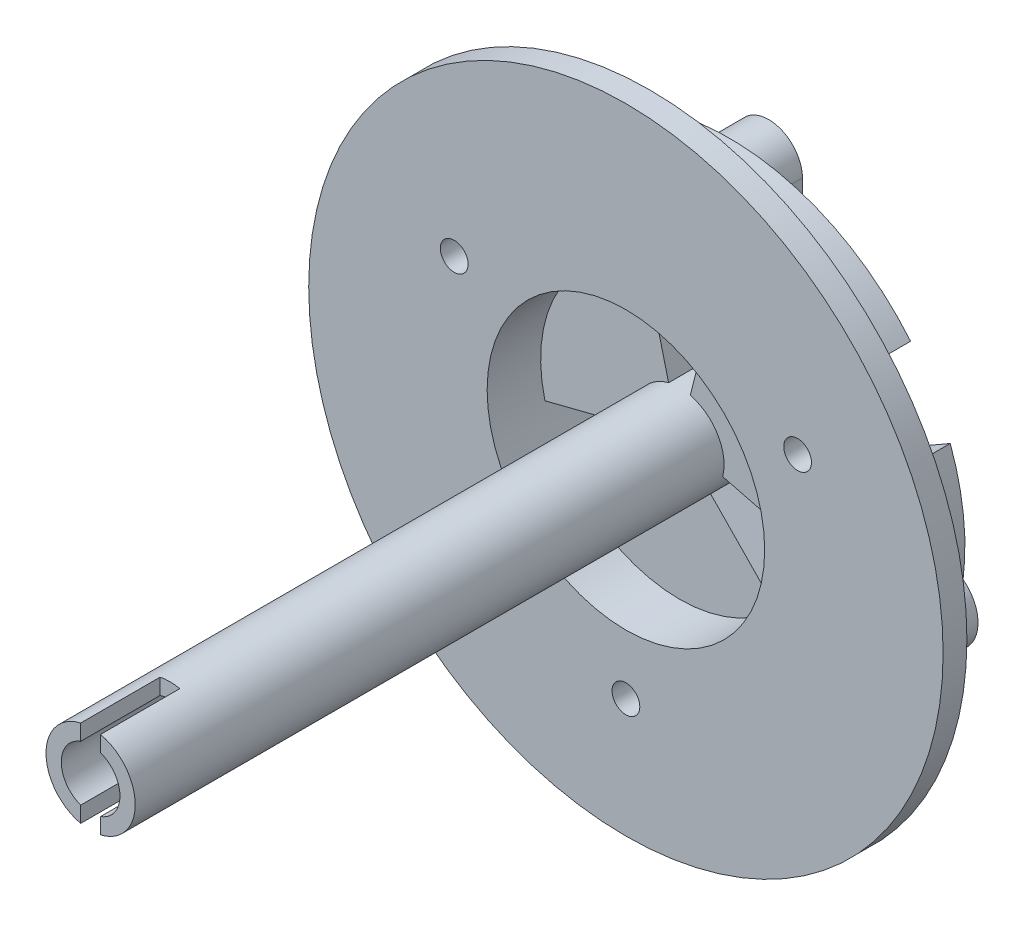
SolidWorks part; units mm, degrees
ref_plane "前视基准面" through (0, 0, 0) normal (0, 0, 1) x (1, 0, 0)
ref_plane "上视基准面" through (0, 0, 0) normal (0, 1, 0) x (1, 0, 0)
ref_plane "右视基准面" through (0, 0, 0) normal (1, 0, 0) x (0, 0, -1)
sketch "草图1" plane through (0, 0, 0) normal (0, 0, 1) x (1, 0, 0)
  circle A0 centre (0, 0) radius 16
extrude "凸台-拉伸1" add sketch "草图1" along normal blind 1.2
sketch "草图2" plane through (0, 0, 1.2) normal (0, 0, 1) x (1, 0, 0)
  circle A0 centre (0, 0) radius 7
extrude "切除-拉伸1" cut sketch "草图2" against normal blind 1.2
sketch "草图3" plane through (0, 0, 1.2) normal (0, 0, 1) x (1, 0, 0)
  circle A2 centre (8.6603, 5) radius 0.7
  circle A3 centre (0, -10) radius 0.7
  circle A4 centre (-8.6603, 5) radius 0.7
extrude "切除-拉伸2" cut sketch "草图3" against normal blind 1.2
sketch "草图4" plane through (0, 0, 0) normal (0, 0, -1) x (-1, 0, 0)
  line L3 (1.7039, 10) -> (1.7039, 5.3952)
  line L16 (-5.5379, -1.0034) -> (-3.6379, -4.2943)
  line L17 (3.6379, -4.2943) -> (5.5379, -1.0034)
  line L18 (1.7039, 5.3952) -> (-1.7039, 5.3952)
  line L19 (-5.5379, -1.0034) -> (-9.6103, -3.3546)
  line L21 (3.6379, -4.2943) -> (7.7103, -6.6454)
  line L25 (-3.6379, -4.2943) -> (-7.7103, -6.6454)
  line L31 (5.5379, -1.0034) -> (9.6103, -3.3546)
  line L32 (-1.7039, 5.3952) -> (-1.7039, 10)
  circle A1 centre (8.6603, -5) radius 0.9
  circle A2 centre (-8.6603, -5) radius 0.9
  circle A3 centre (0, 10) radius 0.9
  arc A4 (1.7039, 10) -> (-1.7039, 10) centre (0, 10) ccw
  arc A5 (7.7103, -6.6454) -> (9.6103, -3.3546) centre (8.6603, -5) ccw
  arc A6 (-9.6103, -3.3546) -> (-7.7103, -6.6454) centre (-8.6603, -5) ccw
extrude "凸台-拉伸2" add sketch "草图4" along normal blind 6
sketch "草图5" plane through (0, 0, 1.2) normal (0, 0, 1) x (1, 0, 0)
  circle A0 centre (0, 0) radius 7
extrude "切除-拉伸3" cut sketch "草图5" against normal blind 11
sketch "草图6" plane through (0, 0, 0) normal (0, 0, -1) x (-1, 0, 0)
  circle A0 centre (0, 0) radius 11.9
  circle A1 centre (0, 0) radius 7
extrude "凸台-拉伸3" add sketch "草图6" along normal blind 4
sketch "草图7" plane through (0, 0, 1.2) normal (0, 0, 1) x (1, 0, 0)
  circle A0 centre (-8.6603, 5) radius 0.7
  circle A1 centre (8.6603, 5) radius 0.7
  circle A2 centre (0, -10) radius 0.7
extrude "切除-拉伸4" cut sketch "草图7" against normal blind 13
sketch "草图8" plane through (0, 0, -4) normal (0, 0, -1) x (-1, 0, 0)
  circle A0 centre (0, 0) radius 2.25
extrude "凸台-拉伸4" add sketch "草图8" against normal blind 33 separate body
sketch "草图9" plane through (0, 0, -4) normal (0, 0, -1) x (-1, 0, 0)
  line L0 (-1.57, -1.6117) -> (-4.8846, -5.0141)
  line L1 (1.57, -1.6117) -> (4.8846, -5.0141)
  line L2 (-2.1808, -0.5539) -> (-6.7846, -1.7232)
  line L3 (-0.5477, 2.1823) -> (-1.7039, 6.7895)
  line L4 (0.5477, 2.1823) -> (1.7039, 6.7895)
  line L5 (2.1808, -0.5539) -> (6.7846, -1.7232)
  arc A0 (-4.8846, -5.0141) -> (4.8846, -5.0141) centre (0, 0) ccw
  arc A1 (-1.7039, 6.7895) -> (-6.7846, -1.7232) centre (0, 0) ccw
  arc A2 (6.7846, -1.7232) -> (1.7039, 6.7895) centre (0, 0) ccw
  arc A3 (2.1808, -0.5539) -> (0.5477, 2.1823) centre (0, 0) ccw
  arc A4 (-1.57, -1.6117) -> (1.57, -1.6117) centre (0, 0) ccw
  arc A5 (-0.5477, 2.1823) -> (-2.1808, -0.5539) centre (0, 0) ccw
extrude "凸台-拉伸5" add sketch "草图9" against normal blind 2.5
sketch "草图10" plane through (0, 0, -4) normal (0, 0, -1) x (-1, 0, 0)
  circle A0 centre (0, 0) radius 1.5
extrude "切除-拉伸5" cut sketch "草图10" against normal blind 33.5
sketch "草图12" plane through (0, 0, 0) normal (1, 0, 0) x (0, 0, -1)
  line L3 (-19.95, -5.0897) -> (-33.7637, -5.0897)
  line L4 (-19.95, -5.0897) -> (-19.95, 5.3715)
  line L5 (-19.95, 5.3715) -> (-33.7637, 5.3715)
  line L6 (-33.7637, -5.0897) -> (-33.7637, 5.3715)
extrude "切除-拉伸6" cut sketch "草图12" against normal mid plane 33.5
sketch "草图13" plane through (0, 0, -4) normal (0, 0, -1) x (-1, 0, 0)
  circle A0 centre (0, -10) radius 2
  circle A1 centre (8.6603, 5) radius 2
  circle A2 centre (-8.6603, 5) radius 2
extrude "切除-拉伸7" cut sketch "草图13" against normal blind 1.5
sketch "草图14" plane through (0, 0, 19.95) normal (0, 0, 1) x (1, 0, 0)
  circle A0 centre (0, 0) radius 1.5
  circle A1 centre (0, 0) radius 2.25
extrude "凸台-拉伸6" add sketch "草图14" along normal blind 8.25
sketch "草图16" plane through (0, 0, -4) normal (0, 0, -1) x (-1, 0, 0)
  line L3 (0, -10) -> (-2, -10)
  line L4 (-2, -10) -> (-2, -14.1303)
  line L5 (-2, -14.1303) -> (2, -14.1303)
  line L6 (2, -14.1303) -> (2, -10)
  line L7 (2, -10) -> (0, -10)
  line L8 (-9.6603, 3.2679) -> (-8.6603, 5)
  line L9 (-8.6603, 5) -> (-7.6603, 6.7321)
  line L10 (-7.6603, 6.7321) -> (-11.2372, 8.7972)
  line L11 (-11.2372, 8.7972) -> (-13.2372, 5.3331)
  line L12 (-13.2372, 5.3331) -> (-9.6603, 3.2679)
  line L13 (7.6603, 6.7321) -> (8.6603, 5)
  line L14 (8.6603, 5) -> (9.6603, 3.2679)
  line L15 (9.6603, 3.2679) -> (13.2372, 5.3331)
  line L16 (13.2372, 5.3331) -> (11.2372, 8.7972)
  line L17 (11.2372, 8.7972) -> (7.6603, 6.7321)
  arc A0 (0.681, -11.8805) -> (-0.681, -11.8805) centre (0, -10) ccw construction
  arc A1 (0.681, -11.8805) -> (-0.681, -11.8805) centre (0, -10) ccw construction
  point P26 (0, 0)
  dimension "D1" = 3
extrude "切除-拉伸9" cut sketch "草图16" against normal blind 1.5
sketch "草图17" plane through (0, 0, 28.2) normal (0, 0, 1) x (1, 0, 0)
  circle A0 centre (0, 0) radius 1.5
  circle A1 centre (0, 0) radius 1.48
extrude "凸台-拉伸7" add sketch "草图17" against normal blind 32.2
sketch "草图15" plane through (0, 0, 28.2) normal (0, 0, 1) x (1, 0, 0)
  line L2 (0.5, 0) -> (0.5, 3.0915)
  line L3 (0.5, 3.0915) -> (-0.5, 3.0915)
  line L4 (-0.5, 3.0915) -> (-0.5, -2.9006)
  line L5 (-0.5, -2.9006) -> (0.5, -2.9006)
  line L6 (0.5, -2.9006) -> (0.5, 0)
extrude "切除-拉伸8" cut sketch "草图15" against normal blind 4
